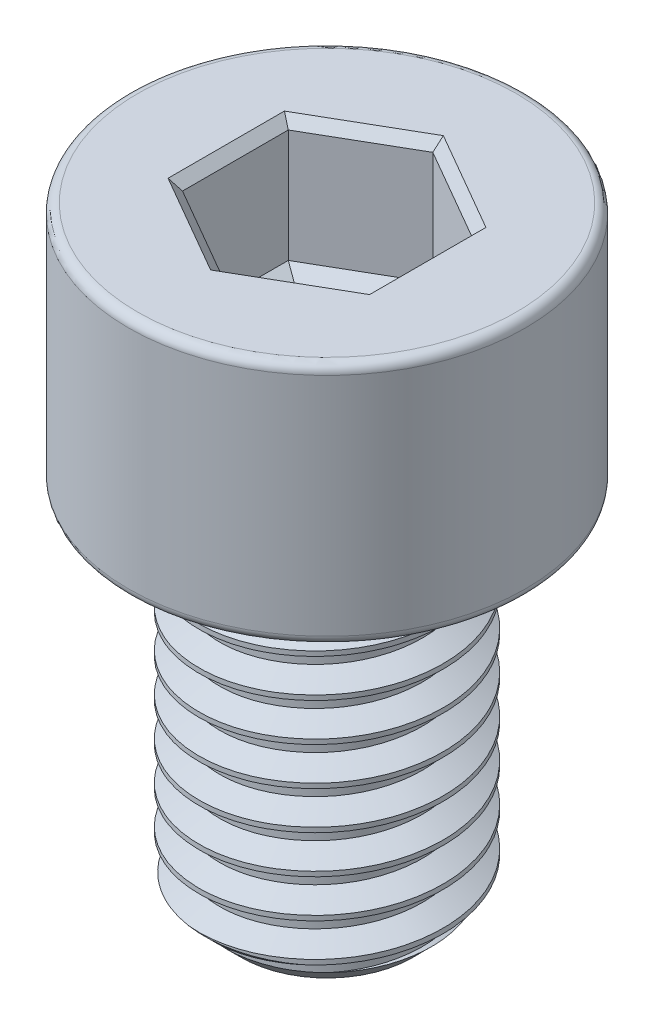
SolidWorks part; units mm, degrees
material "AISI Type A2 Tool Steel"
ref_plane "Front Plane" through (0, 0, 0) normal (0, 0, 1) x (1, 0, 0)
ref_plane "Top Plane" through (0, 0, 0) normal (0, 1, 0) x (1, 0, 0)
ref_plane "Right Plane" through (0, 0, 0) normal (1, 0, 0) x (0, 0, -1)
sketch "Sketch1" plane through (0, 0, 0) normal (0, 1, 0) x (1, 0, 0)
  circle A0 centre (0, 0) radius 4
  dimension "D1" = 8
extrude "Boss-Extrude1" add sketch "Sketch1" along normal blind 12
thread "Thread1" pitch 1.25 method cut profile "Thread Profile1" start angle 0, offset 1.25, length 0, pitch 1.25, diameter 8
ref_plane "Plane1" through (-4, 13.25, 0) normal (0, 0, 1) x (-1, 0, 0)
sketch "Thread Profile1" plane through (-4, 13.25, 0) normal (0, 0, 1) x (-1, 0, 0)
  line L0 (0, 0) -> (0, 1.25) construction
  line L11 (0, 0) -> (0, 1.0937)
  line L12 (0, 1.0937) -> (-0.6766, 0.7031)
  line L13 (-0.6766, 0.7031) -> (-0.6766, 0.3906)
  line L15 (-0.6766, 0.3906) -> (0, 0)
  line L17 (-0.6766, 0.5469) -> (0, 0.5469) construction
  point P2 (0, 0)
  dimension "Pitch" = 1.25
  dimension "Profile_Angle" = 60
  dimension "Profile_Land" = 0.3125
  dimension "Profile_Height" = 0.6766
sketch "Sketch2" plane through (0, 12, 0) normal (0, 1, 0) x (1, 0, 0)
  circle A0 centre (0, 0) radius 6.5
  dimension "D1" = 13
extrude "Boss-Extrude2" add sketch "Sketch2" along normal blind 8
sketch "Sketch5" plane through (0, 0, 0) normal (0, 0, 1) x (1, 0, 0)
  line L0 (0, 0) -> (0, 0.9986) construction
  line L1 (0, 0) -> (4.01, 0) construction
  line L2 (4.01, 0) -> (4.01, 1.2)
  line L3 (4.01, 1.2) -> (2.81, 0)
  line L4 (2.81, 0) -> (4.01, 0)
  dimension "D1" = 1.2
  dimension "D2" = 45
  dimension "D3" = 4.01
revolve "Cut-Revolve1" cut sketch "Sketch5" angle 360 about L0
fillet "Fillet1" radius 0.3 2 edges at (0, 20, 6.5) (0, 12, 6.5)
sketch "Sketch6" plane through (0, 20, 0) normal (0, 1, 0) x (1, 0, 0)
  line L1 (0, 3.4641) -> (-3, 1.7321)
  line L2 (-3, 1.7321) -> (-3, -1.7321)
  line L3 (-3, -1.7321) -> (0, -3.4641)
  line L4 (0, -3.4641) -> (3, -1.7321)
  line L5 (3, -1.7321) -> (3, 1.7321)
  line L6 (3, 1.7321) -> (0, 3.4641)
  circle A0 centre (0, 0) radius 3 construction
  dimension "D1" = 6
extrude "Cut-Extrude1" cut sketch "Sketch6" against normal blind 4
chamfer "Chamfer1" distance 0.3 angle 45 6 edges at (-3, 20, 0) (-1.5, 20, 2.5981) (1.5, 20, 2.5981) (3, 20, 0) (1.5, 20, -2.5981) (-1.5, 20, -2.5981)
sketch "Sketch7" plane through (0, 16, 0) normal (0, 1, 0) x (1, 0, 0)
  line L1 (0, 3.4641) -> (-3, 1.7321)
  line L2 (-3, 1.7321) -> (-3, -1.7321)
  line L3 (-3, -1.7321) -> (0, -3.4641)
  line L4 (0, -3.4641) -> (3, -1.7321)
  line L5 (3, -1.7321) -> (3, 1.7321)
  line L6 (3, 1.7321) -> (0, 3.4641)
  circle A0 centre (0, 0) radius 3 construction
extrude "Cut-Extrude2" cut sketch "Sketch7" against normal blind 0.4 draft 60
